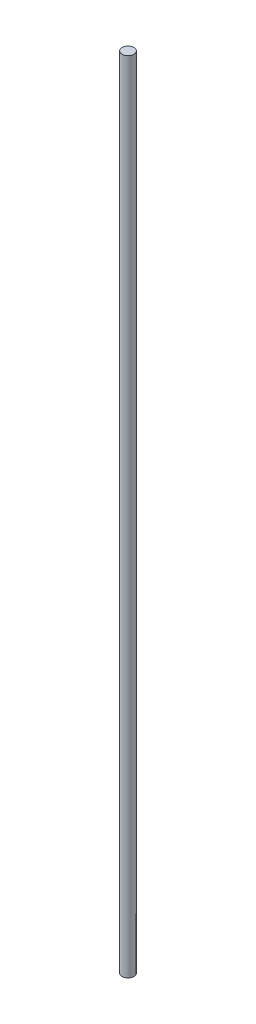
SolidWorks part; units mm, degrees
ref_plane "Front Plane" through (0, 0, 0) normal (0, 0, 1) x (1, 0, 0)
ref_plane "Top Plane" through (0, 0, 0) normal (0, 1, 0) x (1, 0, 0)
ref_plane "Right Plane" through (0, 0, 0) normal (1, 0, 0) x (0, 0, -1)
sketch "Sketch1" plane through (0, 0, 0) normal (0, 1, 0) x (1, 0, 0)
  circle A0 centre (0, 0) radius 4
extrude "Boss-Extrude1" add sketch "Sketch1" along normal blind 538
